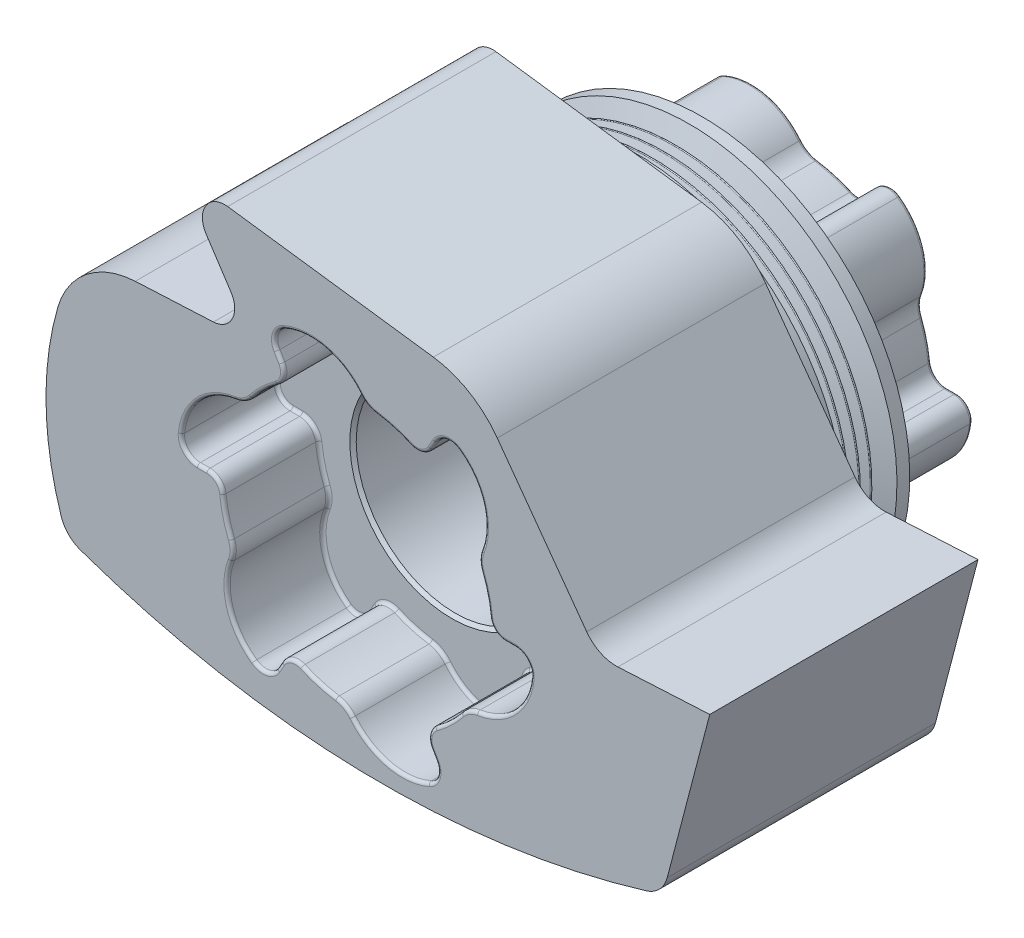
SolidWorks part; units mm, degrees
material "AISI 4340 Aço, normalizado"
ref_plane "Plano frontal" through (0, 0, 0) normal (0, 0, 1) x (1, 0, 0)
ref_plane "Plano superior" through (0, 0, 0) normal (0, 1, 0) x (1, 0, 0)
ref_plane "Plano direito" through (0, 0, 0) normal (1, 0, 0) x (0, 0, -1)
sketch "Esboço1" plane through (0, 0, 0) normal (0, 0, 1) x (1, 0, 0)
  line L0 (111.8543, 17.7809) -> (83.0891, 16.2734)
  line L1 (73.3216, 20.9322) -> (45.3263, 59.4645)
  line L2 (25.3014, 71.4094) -> (-39.0965, 80.0392)
  line L3 (-45.8804, 69.2634) -> (-38.0522, 57.3223)
  line L4 (-43.5654, 46.4928) -> (-68.041, 45.2991)
  line L5 (98.5354, -33.1675) -> (111.8543, 17.7809)
  arc A0 (73.3216, 20.9322) -> (83.0891, 16.2734) centre (82.4956, 27.5975) ccw
  arc A1 (45.3263, 59.4645) -> (25.3014, 71.4094) centre (21.3681, 42.0578) ccw
  arc A2 (-39.0965, 80.0392) -> (-45.8804, 69.2634) centre (-40.0262, 73.1012) ccw
  arc A3 (-43.5654, 46.4928) -> (-38.0522, 57.3223) centre (-43.9064, 53.4845) ccw
  arc A4 (-68.041, 45.2991) -> (-92.3379, 26.0127) centre (-66.7445, 18.718) ccw
  arc A5 (-92.3379, 26.0127) -> (-91.2304, -30.0457) centre (-0.336, -0.2098) ccw
  arc A6 (-91.2304, -30.0457) -> (-85.2361, -36.1673) centre (-82.02, -27.0224) ccw
  arc A7 (-85.2361, -36.1673) -> (91.9754, -39.9908) centre (9.2049, 232.3702) ccw
  arc A8 (91.9754, -39.9908) -> (98.5354, -33.1675) centre (89.1567, -30.7157) ccw
extrude "RESSALTO PRINCIPAL ARMA" add sketch "Esboço1" along normal blind 84 contours L4 A4 A5 A6 A7 A8 L5 L0 A0 L1 A1 L2 A2 L3 A3
sketch "Esboço2" plane through (0, 0, 84) normal (0, 0, 1) x (1, 0, 0)
  circle A0 centre (1.15, 5.38) radius 20
  circle A1 centre (1.15, 5.38) radius 31
  point P2 (0, 0)
  dimension "D3" = 62
  dimension "D4" = 40
  dimension "D2" = 5.38
  dimension "D1" = 1.15
extrude "FURO EIXO" cut sketch "Esboço2" against normal through all contours A0
ref_plane "PLANO (COINC. EIXO ROTAÇÃO)" through (1.15, 0, 0) normal (1, 0, 0) x (0, 0, -1)
sketch "Esboço5" plane through (1.15, 0, 0) normal (1, 0, 0) x (0, 0, -1)
  line L0 (24.3346, 70.38) -> (20.3346, 70.38)
  line L1 (20.3346, 70.38) -> (17.9772, 63.9029)
  line L2 (17.0375, 63.9029) -> (15.9622, 66.8571)
  line L3 (15.4924, 66.8571) -> (14.4172, 63.9029)
  line L4 (13.4775, 63.9029) -> (12.4022, 66.8571)
  line L5 (11.9324, 66.8571) -> (10.8572, 63.9029)
  line L6 (9.9175, 63.9029) -> (8.8422, 66.8571)
  line L7 (8.3724, 66.8571) -> (7.2972, 63.9029)
  line L8 (6.3575, 63.9029) -> (4, 70.38)
  line L9 (4, 70.38) -> (0, 70.38)
  line L10 (0, 70.38) -> (0, 5.38) construction
  line L11 (0, 5.38) -> (24.3346, 5.38) construction
  line L12 (24.3346, 70.38) -> (24.3346, 5.38) construction
  line L13 (-9.0219, 65.38) -> (12.3228, 65.38) construction
  line L14 (0, 20.9322) -> (0, 59.4645) construction
  line L16 (0, 5.38) -> (-84, 5.38) construction
  line L18 (0, 25.38) -> (24.3346, 25.38)
  line L19 (0, -14.62) -> (0, 25.38) construction
  line L20 (24.3346, 70.38) -> (24.3346, 25.38)
  line L21 (0, 70.38) -> (0, 25.38)
  arc A0 (17.9772, 63.9029) -> (17.0375, 63.9029) centre (17.5073, 64.0739) cw
  arc A1 (14.4172, 63.9029) -> (13.4775, 63.9029) centre (13.9473, 64.0739) cw
  arc A2 (10.8572, 63.9029) -> (9.9175, 63.9029) centre (10.3873, 64.0739) cw
  arc A3 (7.2972, 63.9029) -> (6.3575, 63.9029) centre (6.8273, 64.0739) cw
  arc A4 (15.9622, 66.8571) -> (15.4924, 66.8571) centre (15.7273, 66.7716) ccw
  arc A5 (12.4022, 66.8571) -> (11.9324, 66.8571) centre (12.1673, 66.7716) ccw
  arc A6 (8.8422, 66.8571) -> (8.3724, 66.8571) centre (8.6073, 66.7716) ccw
  point P22 (14.9548, 65.38)
  point P29 (16.4999, 65.38)
  point P31 (12.9399, 65.38)
  dimension "D5" = 0.25
  dimension "D6" = 0.5
  dimension "D1" = 40
  dimension "D4" = 3.56
  dimension "D7" = 60
  dimension "D8" = 5
  dimension "D2" = 4
revolve "REVOLUÇÃO POLIA" add sketch "Esboço5" angle 360 about L11
fillet "FILETE REVOLUÇÃO POLIA" radius 1 2 edges at (55.5511, 40.9541, 0) (-63.0753, -4.6254, 0)
fillet "FILETE REVOLUÇÃO POLIA 2" [suppressed] radius 1
sketch "Esboço6" plane through (0, 0, -24.3346) normal (0, 0, -1) x (-1, 0, 0)
  line L0 (-47.8833, 5.38) -> (-50.8994, 5.38)
  line L1 (-24.5166, 45.8522) -> (-26.0247, 48.4642)
  line L2 (22.2166, 45.8522) -> (23.7247, 48.4642)
  line L3 (45.5833, 5.38) -> (48.5994, 5.38)
  line L4 (22.2166, -35.0922) -> (23.7247, -37.7042)
  line L5 (-24.5166, -35.0922) -> (-26.0247, -37.7042)
  arc A0 (-33.9881, -20.8051) -> (-25.9003, -28.5526) centre (-1.15, 5.38) ccw
  arc A1 (-50.8994, 5.38) -> (-55.8743, -0.12) centre (-50.8994, 0.38) ccw
  arc A2 (-47.8833, 5.38) -> (-42.9117, 9.8481) centre (-47.8833, 10.38) ccw
  arc A3 (-55.8743, -0.12) -> (-39.0234, -17.8862) centre (-35.9746, 1.88) ccw
  arc A4 (-33.9881, -20.8051) -> (-39.0234, -17.8862) centre (-40.243, -25.7927) ccw
  circle A30 centre (-1.15, 5.38) radius 55 construction
  arc A33 (-24.5166, 45.8522) -> (-18.1614, 43.7807) centre (-20.1865, 48.3522) ccw
  arc A34 (-26.0247, 48.4642) -> (-33.2753, 50.0226) centre (-30.3548, 45.9642) ccw
  arc A35 (-33.2753, 50.0226) -> (-40.2359, 26.5462) centre (-21.5934, 33.789) ccw
  arc A36 (-40.246, 20.7261) -> (-40.2359, 26.5462) centre (-47.6929, 23.6491) ccw
  arc A37 (22.2166, 45.8522) -> (23.6003, 39.3126) centre (26.5468, 43.3522) ccw
  arc A38 (23.7247, 48.4642) -> (21.449, 55.5226) centre (19.3946, 50.9642) ccw
  arc A39 (21.449, 55.5226) -> (-2.3624, 49.8125) centre (13.2312, 37.289) ccw
  arc A40 (-7.4079, 46.9112) -> (-2.3624, 49.8125) centre (-8.5999, 54.8219) ccw
  arc A41 (45.5833, 5.38) -> (40.6117, 0.9119) centre (45.5833, 0.38) ccw
  arc A42 (48.5994, 5.38) -> (53.5743, 10.88) centre (48.5994, 10.38) ccw
  arc A43 (53.5743, 10.88) -> (36.7234, 28.6462) centre (33.6746, 8.88) ccw
  arc A44 (31.6881, 31.5651) -> (36.7234, 28.6462) centre (37.943, 36.5527) ccw
  arc A45 (22.2166, -35.0922) -> (15.8614, -33.0207) centre (17.8865, -37.5922) ccw
  arc A46 (23.7247, -37.7042) -> (30.9753, -39.2626) centre (28.0548, -35.2042) ccw
  arc A47 (30.9753, -39.2626) -> (37.9359, -15.7862) centre (19.2934, -23.029) ccw
  arc A48 (37.946, -9.9661) -> (37.9359, -15.7862) centre (45.3929, -12.8891) ccw
  arc A49 (-24.5166, -35.0922) -> (-25.9003, -28.5526) centre (-28.8468, -32.5922) ccw
  arc A50 (-26.0247, -37.7042) -> (-23.749, -44.7626) centre (-21.6946, -40.2042) ccw
  arc A51 (-23.749, -44.7626) -> (0.0624, -39.0525) centre (-15.5312, -26.529) ccw
  arc A52 (5.1079, -36.1512) -> (0.0624, -39.0525) centre (6.2999, -44.0619) ccw
  arc A53 (-40.246, 20.7261) -> (-42.9117, 9.8481) centre (-1.15, 5.38) ccw
  arc A54 (-7.4079, 46.9112) -> (-18.1614, 43.7807) centre (-1.15, 5.38) ccw
  arc A55 (31.6881, 31.5651) -> (23.6003, 39.3126) centre (-1.15, 5.38) ccw
  arc A56 (37.946, -9.9661) -> (40.6117, 0.9119) centre (-1.15, 5.38) ccw
  arc A57 (5.1079, -36.1512) -> (15.8614, -33.0207) centre (-1.15, 5.38) ccw
  circle A58 centre (-1.15, 5.38) radius 20
  circle A59 centre (-1.15, 5.38) radius 20 construction
  point P48 (-1.15, 5.38)
  dimension "D1" = 5
  dimension "D4" = 8
  dimension "D3" = 5
  dimension "D5" = 20
  dimension "D2" = 110
  dimension "D7" = 13
  dimension "D6" = 6
extrude "RESSALTO CAMISA" add sketch "Esboço6" along normal blind 30
extrude "REBAIXO ROLAMENTO CAMISA" cut sketch "Esboço2<4>" along normal blind 20 from surface contours A1 starting at face at (1.15, 5.38, -54.3346)
sketch "Esboço2<4>" plane through (0, 0, 84) normal (0, 0, 1) x (1, 0, 0) same geometry as "Esboço2"
fillet "FILETE RESSALTO CAMISA" radius 1 72 edges at (4.612, 47.8867, -24.3346) (-8.5673, 56.7375, -24.3346) (-24.1533, 52.4985, -24.3346) (-22.9707, 47.1582, -24.3346) (-21.6551, 42.3172, -24.3346) (-27.9036, 35.7097, -24.3346) (-33.9309, 29.6315, -24.3346) (-48.1856, 22.6434, -24.3346) (-52.3075, 7.0259, -24.3346) (-47.0913, 5.38, -24.3346) (-42.2411, 4.0988, -24.3346) (-39.6431, -4.6163, -24.3346) (-37.3929, -12.8752, -24.3346) (-38.4683, -28.7142, -24.3346) (-27.0041, -40.0926, -24.3346) (-22.9707, -36.3982, -24.3346) (-19.436, -32.8384, -24.3346) (-10.5895, -34.946, -24.3346) (-2.312, -37.1267, -24.3346) (10.8673, -45.9775, -24.3346) (26.4533, -41.7385, -24.3346) (25.2707, -36.3982, -24.3346) (23.9551, -31.5572, -24.3346) (30.2036, -24.9497, -24.3346) (36.2309, -18.8715, -24.3346) (50.4856, -11.8834, -24.3346) (54.6075, 3.7341, -24.3346) (49.3913, 5.38, -24.3346) (44.5411, 6.6612, -24.3346) (41.9431, 15.3763, -24.3346) (39.6929, 23.6352, -24.3346) (40.7683, 39.4742, -24.3346) (29.3041, 50.8526, -24.3346) (25.2707, 47.1582, -24.3346) (21.736, 43.5984, -24.3346) (12.8895, 45.706, -24.3346) (39.6929, 23.6352, -54.3346) (40.7683, 39.4742, -54.3346) (29.3041, 50.8526, -54.3346) (25.2707, 47.1582, -54.3346) (21.736, 43.5984, -54.3346) (12.8895, 45.706, -54.3346) (4.612, 47.8867, -54.3346) (-8.5673, 56.7375, -54.3346) (-24.1533, 52.4985, -54.3346) (-22.9707, 47.1582, -54.3346) (-21.6551, 42.3172, -54.3346) (-27.9036, 35.7097, -54.3346) (-33.9309, 29.6315, -54.3346) (-48.1856, 22.6434, -54.3346) (-52.3075, 7.0259, -54.3346) (-47.0913, 5.38, -54.3346) (-42.2411, 4.0988, -54.3346) (-39.6431, -4.6163, -54.3346) (-37.3929, -12.8752, -54.3346) (-38.4683, -28.7142, -54.3346) (-27.0041, -40.0926, -54.3346) (-22.9707, -36.3982, -54.3346) (-19.436, -32.8384, -54.3346) (-10.5895, -34.946, -54.3346) (-2.312, -37.1267, -54.3346) (10.8673, -45.9775, -54.3346) (26.4533, -41.7385, -54.3346) (25.2707, -36.3982, -54.3346) (23.9551, -31.5572, -54.3346) (30.2036, -24.9497, -54.3346) (36.2309, -18.8715, -54.3346) (50.4856, -11.8834, -54.3346) (54.6075, 3.7341, -54.3346) (49.3913, 5.38, -54.3346) (44.5411, 6.6612, -54.3346) (41.9431, 15.3763, -54.3346)
chamfer "CHANFRO ROLAMENTO CAMISA" distance 1 angle 45 1 edges at (1.15, 36.38, -54.3346)
fillet "FILETE REBAIXO ROLAMENTO CAMISA" radius 1 1 edges at (1.15, 36.38, -34.3346)
sketch "Esboço8" plane through (0, 0, 0) normal (0, 0, -1) x (-1, 0, 0)
  circle A0 centre (-1.15, 5.38) radius 111.3967
extrude "CORTE ARMA III" [suppressed] cut sketch "Esboço8" along normal through all
extrude "REBAIXO ROLAMENTO" cut sketch "Esboço2<5>" against normal blind 60
sketch "Esboço2<5>" plane through (0, 0, 84) normal (0, 0, 1) x (1, 0, 0) same geometry as "Esboço2"
chamfer "CHANFRO REBAIXO ROLAMENTO" [suppressed] distance 1 angle 45
fillet "FILETE REBAIXO ROLAMENTO" radius 1 1 edges at (32.15, 5.38, 24)
extrude "REBAIXO CAMISA" cut sketch "Esboço6<2>" along normal blind 30 from surface starting at face at (32.15, 5.38, 84)
sketch "Esboço6<2>" plane through (0, 0, -24.3346) normal (0, 0, -1) x (-1, 0, 0) same geometry as "Esboço6"
fillet "FILETE REBAIXO CAMISA" radius 1 72 edges at (-33.9309, 29.6315, 54) (-27.9036, 35.7097, 54) (-21.6551, 42.3172, 54) (-22.9707, 47.1582, 54) (-24.1533, 52.4985, 54) (-8.5673, 56.7375, 54) (4.612, 47.8867, 54) (12.8895, 45.706, 54) (21.736, 43.5984, 54) (25.2707, 47.1582, 54) (29.3041, 50.8526, 54) (40.7683, 39.4742, 54) (39.6929, 23.6352, 54) (41.9431, 15.3763, 54) (44.5411, 6.6612, 54) (49.3913, 5.38, 54) (54.6075, 3.7341, 54) (50.4856, -11.8834, 54) (36.2309, -18.8715, 54) (30.2036, -24.9497, 54) (23.9551, -31.5572, 54) (25.2707, -36.3982, 54) (26.4533, -41.7385, 54) (10.8673, -45.9775, 54) (-2.312, -37.1267, 54) (-10.5895, -34.946, 54) (-19.436, -32.8384, 54) (-22.9707, -36.3982, 54) (-27.0041, -40.0926, 54) (-38.4683, -28.7142, 54) (-37.3929, -12.8752, 54) (-39.6431, -4.6163, 54) (-42.2411, 4.0988, 54) (-47.0913, 5.38, 54) (-52.3075, 7.0259, 54) (-33.9309, 29.6315, 84) (-27.9036, 35.7097, 84) (-21.6551, 42.3172, 84) (-22.9707, 47.1582, 84) (-24.1533, 52.4985, 84) (-8.5673, 56.7375, 84) (4.612, 47.8867, 84) (12.8895, 45.706, 84) (21.736, 43.5984, 84) (25.2707, 47.1582, 84) (29.3041, 50.8526, 84) (40.7683, 39.4742, 84) (39.6929, 23.6352, 84) (41.9431, 15.3763, 84) (44.5411, 6.6612, 84) (49.3913, 5.38, 84) (54.6075, 3.7341, 84) (50.4856, -11.8834, 84) (36.2309, -18.8715, 84) (30.2036, -24.9497, 84) (23.9551, -31.5572, 84) (25.2707, -36.3982, 84) (26.4533, -41.7385, 84) (10.8673, -45.9775, 84) (-2.312, -37.1267, 84) (-10.5895, -34.946, 84) (-19.436, -32.8384, 84) (-22.9707, -36.3982, 84) (-27.0041, -40.0926, 84) (-38.4683, -28.7142, 84) (-37.3929, -12.8752, 84) (-39.6431, -4.6163, 84) (-42.2411, 4.0988, 84) (-47.0913, 5.38, 84) (-52.3075, 7.0259, 84) (-48.1856, 22.6434, 54) (-48.1856, 22.6434, 84)
extrude "REBAIXO ROLAMENTO ARMA II" cut sketch "Esboço2<6>" against normal blind 40 from surface starting at face at (1.15, 5.38, 54)
sketch "Esboço2<6>" plane through (0, 0, 84) normal (0, 0, 1) x (1, 0, 0) same geometry as "Esboço2"
chamfer "CHANFRO REBAIXO ARMA II" distance 1 angle 45 1 edges at (32.15, 5.38, 54)
equation "\"arma_B\"=84"
equation "\"D1@RESSALTO PRINCIPAL ARMA\" = \"arma_B\""
equation "\"rolamento_ext\"= 62"
equation "\"D3@Esboço2\"=\"rolamento_ext\""
equation "\"rolamento_int\"= 35"
equation "\"rolamento_esp\"= 20"
equation "\"D1\"= 3 * \"rolamento_esp\""
equation "\"arma_eixo_dist\"= 5"
equation "\"esp_rolamento_camisa\"=12"
equation "\"D4@Esboço2\"=\"rolamento_int\"+\"arma_eixo_dist\""
equation "\"D1@REBAIXO ROLAMENTO CAMISA\" = \"rolamento_esp\""
equation "\"D1@RESSALTO CAMISA\"=\"rolamento_esp\" + 10"
equation "\"polia_parede\"=4"
equation "\"D2@Esboço5\"=\"polia_parede\""
equation "\"polia_altura\"=5"
equation "\"D8@Esboço5\"=\"polia_altura\""
equation "\"polia_angulo\"=40"
equation "\"D1@Esboço5\"=\"polia_angulo\""
equation "\"polia_diam_eff\"=60"
equation "\"D7@Esboço5\"=\"polia_diam_eff\""
equation "\"polia_passo\"=3.56"
equation "\"D4@Esboço5\"=\"polia_passo\""
equation "\"D2@Esboço2\"=\"SW-CentrodaMassaY\""
equation "\"D1@Esboço2\"=\"SW-CentrodaMassaX\""
equation "\"D1@REBAIXO ROLAMENTO\" = 3 * \"rolamento_esp\""
equation "\"A\"=60"
equation "\"camisa_diam_ext\"=110"
equation "\"D2@Esboço6\"=\"camisa_diam_ext\""
